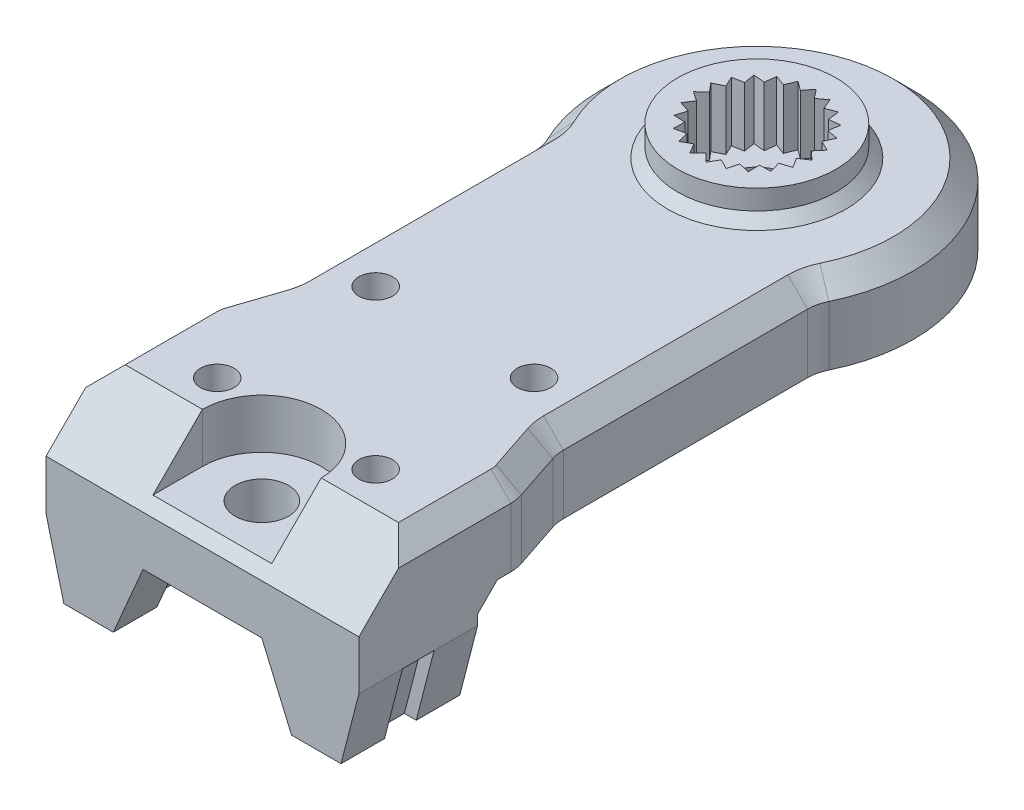
SolidWorks part; units mm, degrees
material "ABS"
ref_plane "正面" through (0, 0, 0) normal (0, 0, 1) x (1, 0, 0)
ref_plane "平面" through (0, 0, 0) normal (0, 1, 0) x (1, 0, 0)
ref_plane "右側面" through (0, 0, 0) normal (1, 0, 0) x (0, 0, -1)
sketch "ｽｹｯﾁ1" plane through (0, 0, 0) normal (0, 1, 0) x (1, 0, 0)
  line L2 (-7.9, 0) -> (-7.9, -28)
  line L3 (-7.9, -28) -> (7.9, -28)
  line L4 (7.9, 0) -> (7.9, -28)
  line L5 (-7.9, 0) -> (7.9, -28) construction
  line L6 (-7.9, -28) -> (7.9, 0) construction
  arc A0 (7.9, 0) -> (-7.9, 0) centre (0, 0) ccw
  point P7 (0, -14)
  dimension "D4" = 28
  dimension "D3" = 15.8
extrude "ﾎﾞｽ - 押し出し1" add sketch "ｽｹｯﾁ1" along normal blind 4
sketch "ｽｹｯﾁ4" plane through (0, 0, 28) normal (0, 0, 1) x (1, 0, 0)
  line L1 (-7, -5) -> (-4.5, -5)
  line L2 (-4.5, -5) -> (-3, -1.5)
  line L3 (-3, -1.5) -> (3, -1.5)
  line L4 (3, -1.5) -> (4.5, -5)
  line L5 (4.5, -5) -> (7, -5)
  line L7 (7.9, 0) -> (-7.9, 0)
  line L8 (7, -5) -> (7.9, -1.5)
  line L9 (7.9, -1.5) -> (7.9, 0)
  line L10 (-7, -5) -> (-7.9, -1.5)
  line L11 (-7.9, -1.5) -> (-7.9, 0)
  dimension "D1" = 5
  dimension "D2" = 3.5
  dimension "D3" = 3
  dimension "D4" = 7
  dimension "D5" = 2.5
  dimension "D9" = 1.5
  dimension "D10" = 1.5
extrude "ﾎﾞｽ - 押し出し3" add sketch "ｽｹｯﾁ4" against normal blind 6
chamfer "面取り1" distance 3 angle 45 1 edges at (0, 4, 28)
sketch "ｽｹｯﾁ5" plane through (0, 4, 0) normal (0, 1, 0) x (1, 0, 0)
  line L0 (-4, -23.25) -> (4, -23.25) construction
  line L1 (7.9, -28) -> (-7.9, -28) construction
  circle A0 centre (-4, -23.25) radius 0.85
  circle A1 centre (4, -23.25) radius 0.85
  dimension "D1" = 1.7
  dimension "D2" = 1.7
  dimension "D4" = 4
  dimension "D3" = 8
  dimension "D5" = 4.75
extrude "ｶｯﾄ - 押し出し1" cut sketch "ｽｹｯﾁ5" against normal blind 4
pattern_linear "直線ﾊﾟﾀｰﾝ1" count 2 spacing 8 along (0, 0, -1) of "ｶｯﾄ - 押し出し1"
sketch "ｽｹｯﾁ6" plane through (0, 4, 0) normal (0, 1, 0) x (1, 0, 0)
  line L0 (-3, -25) -> (-3, -29)
  line L1 (-3, -29) -> (3, -29)
  line L2 (3, -29) -> (3, -25)
  line L3 (7.9, -28) -> (-7.9, -28) construction
  arc A0 (3, -25) -> (-3, -25) centre (0, -25) ccw
  dimension "D1" = 6
  dimension "D3" = 3
  dimension "D2" = 0
  dimension "D4" = 4
extrude "ｶｯﾄ - 押し出し2" cut sketch "ｽｹｯﾁ6" against normal blind 2.5
sketch "ｽｹｯﾁ7" plane through (0, 1.5, 0) normal (0, 1, 0) x (1, 0, 0)
  circle A0 centre (0, -25) radius 1.35
  dimension "D1" = 2.7
extrude "ｶｯﾄ - 押し出し3" cut sketch "ｽｹｯﾁ7" against normal up to next
sketch "ｽｹｯﾁ9" plane through (0, 0, 0) normal (0, 1, 0) x (1, 0, 0)
  circle A0 centre (0, 0) radius 3.25
  dimension "D1" = 6.5
extrude "ｶｯﾄ - 押し出し4" cut sketch "ｽｹｯﾁ9" along normal blind 1
sketch "ｽｹｯﾁ10" plane through (0, 4, 0) normal (0, 1, 0) x (1, 0, 0)
  circle A0 centre (0, 0) radius 4
  dimension "D1" = 8
extrude "ﾎﾞｽ - 押し出し4" add sketch "ｽｹｯﾁ10" along normal blind 1.5
chamfer "面取り3" distance 0.5 angle 45 1 edges at (0, 4, 4)
sketch "ｽｹｯﾁ11" plane through (0, 5.5, 0) normal (0, 1, 0) x (1, 0, 0)
  circle A0 centre (0, 0) radius 3
  dimension "D1" = 6
extrude "ｶｯﾄ - 押し出し5" cut sketch "ｽｹｯﾁ11" against normal blind 3
sketch "ｽｹｯﾁ12" plane through (0, 1, 0) normal (0, -1, 0) x (1, 0, 0)
  circle A0 centre (0, 0) radius 1.55
  dimension "D1" = 3.1
extrude "ｶｯﾄ - 押し出し6" cut sketch "ｽｹｯﾁ12" against normal through all
sketch "ｽｹｯﾁ13" plane through (0, 5.5, 0) normal (0, 1, 0) x (1, 0, 0)
  line L0 (0.4085, -2.9721) -> (0, -2.5745)
  line L1 (0, -2.5745) -> (-0.4085, -2.9721)
  line L2 (0, 0) -> (0.4085, -2.9721) construction
  line L3 (0, 0) -> (-0.4085, -2.9721) construction
  line L4 (0, -2.5745) -> (0, 0) construction
  circle A0 centre (0, 0) radius 3 construction
  circle A1 centre (0, 0) radius 3 construction
  arc A2 (0.4085, -2.9721) -> (-0.4085, -2.9721) centre (0, 0) cw
  dimension "D1" = 15.652
  dimension "D2" = 0.57
extrude "ﾎﾞｽ - 押し出し5" add sketch "ｽｹｯﾁ13" against normal up to surface (3 mm away) up to face at (0, 2.5, 1.55)
pattern_circular "円形ﾊﾟﾀｰﾝ1" count 23 over 360 about axis through (0, 2.5, 0) along (0, 1, 0) of "ﾎﾞｽ - 押し出し5" reverse direction yes
ref_plane "平面1" through (0, 0, 25) normal (0, 0, 1) x (1, 0, 0)
sketch "ｽｹｯﾁ14" plane through (0, 0, 25) normal (0, 0, 1) x (1, 0, 0)
  line L0 (3, -1.5) -> (4.5, -5)
  line L1 (3, -1.5) -> (3.6, -1.5)
  line L2 (4.5, -5) -> (5.1, -5)
  line L3 (3.6, -1.5) -> (5.1, -5)
  line L4 (3, -1.5) -> (5.1, -5) construction
  line L5 (4.5, -5) -> (3.6, -1.5) construction
  line L6 (4.5, -5) -> (7, -5) construction
  line L7 (6.4, -5) -> (7, -5)
  line L8 (6.4, -5) -> (7.3, -1.5)
  line L9 (7, -5) -> (7.9, -1.5)
  line L10 (7.3, -1.5) -> (7.9, -1.5)
  line L11 (6.4, -5) -> (7.9, -1.5) construction
  line L12 (7, -5) -> (7.3, -1.5) construction
  point P5 (4.05, -3.25)
  point P14 (7.15, -3.25)
  dimension "D1" = 0.6
extrude "ｶｯﾄ - 押し出し7" cut sketch "ｽｹｯﾁ14" against normal mid plane 1.6
mirror "ﾐﾗｰ1" about plane through (0, 0, 0) normal (1, 0, 0) of "ｶｯﾄ - 押し出し7"
sketch "ｽｹｯﾁ15" plane through (0, 4, 0) normal (0, 1, 0) x (1, 0, 0)
  line L0 (-7.9, 0) -> (-7.9, -20)
  line L1 (-7.9, 0) -> (-7.9, -25) construction
  line L2 (-7.9, -20) -> (-6.9, -17)
  line L3 (-6.9, -17) -> (-6.9, -3.8471)
  line L4 (0, -5.775) -> (0, 5.775) construction
  line L5 (7.9, -28) -> (-7.9, -28) construction
  arc A0 (-7.9, 0) -> (-6.9, -3.8471) centre (0, 0) ccw
  arc A1 (7.9, 0) -> (-7.9, 0) centre (0, 0) ccw construction
  dimension "D1" = 6.9
  dimension "D2" = 11
  dimension "D3" = 8
extrude "ｶｯﾄ - 押し出し8" cut sketch "ｽｹｯﾁ15" against normal through all
mirror "ﾐﾗｰ2" about plane through (0, 0, 0) normal (1, 0, 0) of "ｶｯﾄ - 押し出し8"
fillet "ﾌｨﾚｯﾄ1" radius 2 6 edges at (6.9, 2, 3.8471) (7.9, 2, 20) (6.9, 2, 17) (-7.9, 2, 20) (-6.9, 2, 17) (-6.9, 2, 3.8471)
chamfer "面取り2" distance 1 angle 45 14 edges at (-7.9, 4, 22.6623) (0, 4, -7.9) (7.9, 4, 22.6623) (0, 0, 22) (-7.8742, 4, 20.0042) (-7.4, 4, 18.5) (-6.9258, 4, 16.9958) (-6.9, 4, 10.5057) (-6.9512, 4, 3.8864) (6.9512, 4, 3.8864) (6.9, 4, 10.5057) (6.9258, 4, 16.9958) (7.4, 4, 18.5) (7.8742, 4, 20.0042)
ref_axis "軸1" through (0, 3, 0) along (0, -1, 0)
